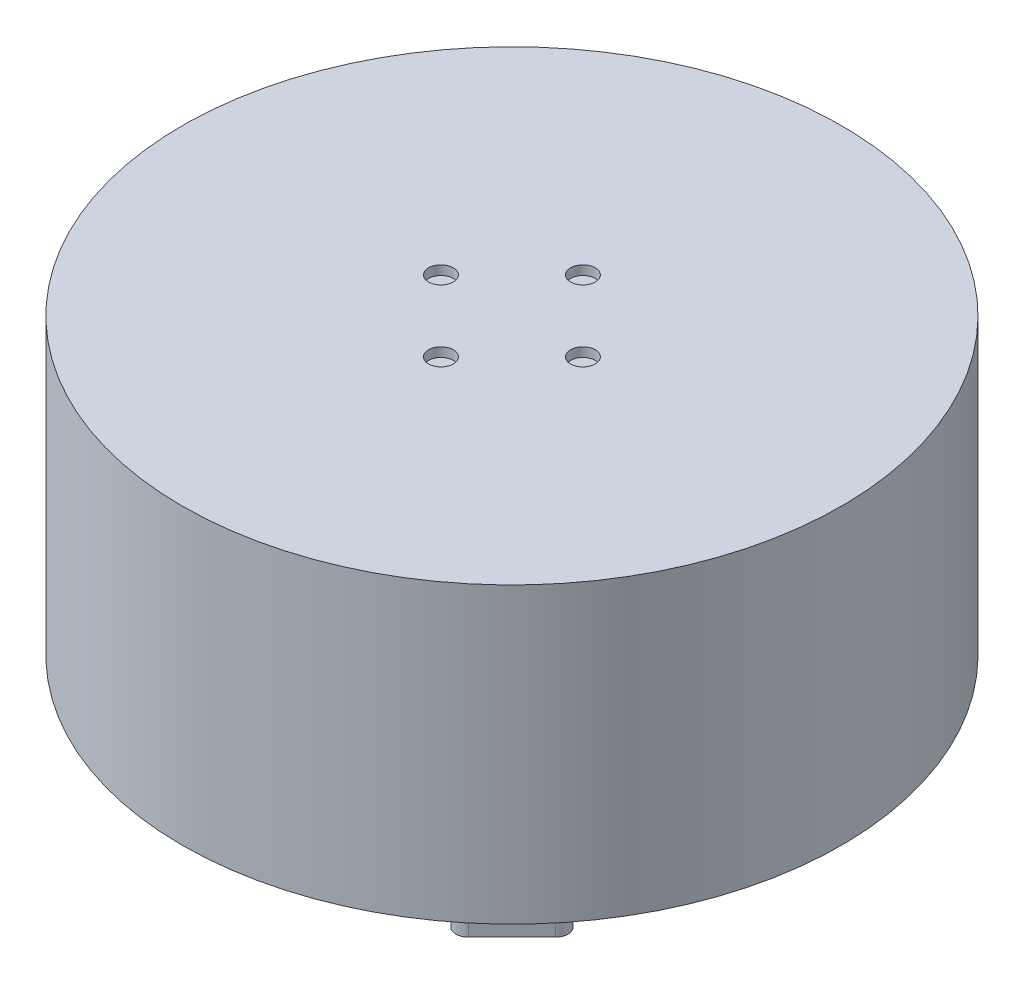
SolidWorks part; units mm, degrees
ref_plane "Front Plane" through (0, 0, 0) normal (0, 0, 1) x (1, 0, 0)
ref_plane "Top Plane" through (0, 0, 0) normal (0, 1, 0) x (1, 0, 0)
ref_plane "Right Plane" through (0, 0, 0) normal (1, 0, 0) x (0, 0, -1)
sketch "Sketch1" plane through (0, 0, 0) normal (0, 1, 0) x (1, 0, 0)
  circle A0 centre (0, 0) radius 53.4
  dimension "D1" = 106.8
extrude "Boss-Extrude1" add sketch "Sketch1" along normal blind 47.6
sketch "Sketch2" plane through (0, 0, 0) normal (0, -1, 0) x (1, 0, 0)
  circle A0 centre (0, 0) radius 20 construction
  circle A1 centre (0, 20) radius 2.5
  circle A2 centre (20, 0) radius 2.5
  circle A3 centre (0, -20) radius 2.5
  circle A4 centre (-20, 0) radius 2.5
  point P14 (0, 0)
  dimension "D1" = 40
  dimension "D2" = 5
  dimension "D3" = 4
extrude "Cut-Extrude1" cut sketch "Sketch2" against normal blind 1.5
sketch "Sketch3" plane through (0, 0, 0) normal (0, -1, 0) x (1, 0, 0)
  line L0 (0, 0) -> (0, 20) construction
  line L1 (0, 20) -> (20, 0) construction
  line L2 (20, 0) -> (0, 0) construction
  line L3 (0, 0) -> (32.1734, 32.1734) construction
  line L4 (28.6378, 35.7089) -> (35.7089, 28.6378) construction
  line L5 (30.7591, 37.8302) -> (37.8302, 30.7591) construction
  line L6 (26.5165, 33.5876) -> (33.5876, 26.5165) construction
  line L7 (30.052, 37.1231) -> (37.1231, 30.052)
  line L8 (27.2236, 34.2947) -> (34.2947, 27.2236)
  arc A0 (30.7591, 37.8302) -> (26.5165, 33.5876) centre (28.6378, 35.7089) ccw construction
  arc A1 (33.5876, 26.5165) -> (37.8302, 30.7591) centre (35.7089, 28.6378) ccw construction
  arc A2 (34.2947, 27.2236) -> (37.1231, 30.052) centre (35.7089, 28.6378) ccw
  arc A3 (30.052, 37.1231) -> (27.2236, 34.2947) centre (28.6378, 35.7089) ccw
  point P9 (32.1734, 32.1734)
  dimension "D3" = 3
  dimension "D1" = 45.5
  dimension "D2" = 10
  dimension "D4" = 1
extrude "Boss-Extrude2" add sketch "Sketch3" along normal blind 6
sketch "Sketch4" plane through (0, 47.6, 0) normal (0, 1, 0) x (1, 0, 0)
  circle A0 centre (0, 0) radius 11.5 construction
  circle A1 centre (0, 11.5) radius 2
  circle A2 centre (11.5, 0) radius 2
  circle A3 centre (0, -11.5) radius 2
  circle A4 centre (-11.5, 0) radius 2
  point P14 (0, 0)
  dimension "D3" = 4
  dimension "D1" = 23
  dimension "D2" = 4
extrude "Cut-Extrude2" cut sketch "Sketch4" against normal blind 1.5
equation "\"Np_b\" = 40"
equation "\"module\" = 0.7"
equation "\"pressure angle\" = 20.0"
equation "\"h_a\" = 0.7"
equation "\"h_b\" = 0.875"
equation "\"clr_tip_root\" = 0.17500000000000004"
equation "\"fw_p_s\" = 25.912913082891553"
equation "\"Nr_s\" = 116"
equation "\"pressure_angle\" = 20.0"
equation "\"h_f\" = 0.875"
equation "\"dp_r_s\" = 81.19999999999999"
equation "\"db_r_s\" = 76.30304080781575"
equation "\"fw_r_s\" = 24.412913082891553"
equation "\"alpha_r_s\" = 0.8539582918412556"
equation "\"beta_r_s\" = 3.259640721613546"
equation "\"bearing_ID\" = 70"
equation "\"bearing_OD\" = 90"
equation "\"bearing_height\" = 10"
equation "\"clearance_planet\" = 1.5"
equation "\"case_dist\" = 6.5"
equation "\"Motor_case_OD_max\" = 131.3"
equation "\"case_mounting_PCD\" = 123.8"
equation "\"bearing mount thickness\" = 8"
equation "\"case_mounting_hole_dia\" = 3"
equation "\"output_mounting_PCD\" = 98"
equation "\"output_mounting_hole_dia\" = 4"
equation "\"clearance_case_mount_holes_shell_thickness\" = 1"
equation "\"motor_case_OD_base\" = 121.8"
equation "\"sec_carrier_thickness\" = 5"
equation "\"sun_coupler_hub_thickness\" = 4"
equation "\"clearance_sun_coupler_sec_carrier\" = 1.5"
equation "\"clearance_motor_and_case\" = 5"
equation "\"motor_OD\" = 106.8"
equation "\"Motor_case_thickness\" = 2.5"
equation "\"Motor_case_ID\" = 116.8"
equation "\"case_mounting_hole_shift\" = 1.0"
equation "\"output_mounting_nut_wrench_size\" = 7"
equation "\"output_mounting_nut_thickness\" = 3.2"
equation "\"case_mounting_hole_allen_socket_dia\" = 5.5"
equation "\"output_mounting_nut_depth\" = 3"
equation "\"case_mounting_bolt_depth\" = 4.5"
equation "\"Ns\" = 48"
equation "\"ring_radial_thickness\" = 5"
equation "\"ring_OD\"= \"Nr_s\" * \"module\" + \"ring_radial_thickness\" * 2"
equation "\"ring_to_chamfer_clearance\" = 1.5"
equation "\"Motor_case_OD_base_to_chamfer\" = 5"
equation "\"pattern_offset_from_motor_case_OD_base\" = 3"
equation "\"pattern_bulge_dia\" = 3"
equation "\"pattern_num_bulge\" = 18"
equation "\"pattern_depth\" = 2"
equation "\"motor_height\" = 47.6"
equation "\"case_mounting_wrench_size\" = 5.5"
equation "\"case_mounting_nut_clearance\" = 2"
equation "\"base_plate_thickness\" = 4"
equation "\"case_mounting_nut_thickness\" = 2.4"
equation "\"case_mounting_surface_height\" = 4"
equation "\"motor_mount_hole_PCD\" = 40"
equation "\"motor_mount_hole_dia\" = 5"
equation "\"motor_mount_hole_num\" = 4"
equation "\"central_hole_offset_from_motor_mount_PCD\" = 5"
equation "\"wire_slot_dist_from_center\" = 45.5"
equation "\"wire_slot_length\" = 10"
equation "\"wire_slot_radius\" = 3"
equation "\"driver_upper_holes_dist_from_center\" = 29"
equation "\"driver_lower_holes_dist_from_center\" = 13"
equation "\"driver_side_holes_dist_from_center\" = 22.5"
equation "\"driver_mount_holes_dia\" = 3"
equation "\"driver_mount_inserts_OD\" = 4.8"
equation "\"driver_mount_thickness\" = 1.5"
equation "\"driver_mount_height\" = 6"
equation "\"air_flow_hole_offset\" = 3"
equation "\"num_planet\" = 4"
equation "\"planet_pin_bolt_dia\" = 5"
equation "\"planet_pin_socket_head_dia\" = 8.5"
equation "\"carrier_PCD\" = 61.599999999999994"
equation "\"planet_shaft_dia\" = 8"
equation "\"planet_shaft_step_offset\" = 1"
equation "\"carrier_trapezoidal_support_sun_offset\" = 5"
equation "\"carrier_trapezoidal_support_hole_PCD_offset_bearing_ID\" = 4"
equation "\"carrier_trapezoidal_support_hole_dia\" = 3"
equation "\"carrier_trapezoidal_support_hole_socket_head_dia\" = 5.5"
equation "\"carrier_bearing_step_width\" = 1.5"
equation "\"standard_clearance_1_5mm\" = 1.5"
equation "\"standard_fillet_1_5mm\" = 1.5"
equation "\"sun_shaft_bearing_OD\" = 16"
equation "\"sun_shaft_bearing_width\" = 5"
equation "\"standard_bearing_insertion_chamfer\" = 0.5"
equation "\"carrier_trapezoidal_support_hole_wrench_size\" = 5.5"
equation "\"planet_pin_bolt_wrench_size\" = 8"
equation "\"planet_bearing_OD\" = 12"
equation "\"planet_bearing_width\" = 3.5"
equation "\"planet_bore\" = 10"
equation "\"D1@Boss-Extrude1\"=\"motor_height\""
equation "\"D1@Sketch1\"=\"motor_OD\""
equation "\"D1@Sketch2\"=\"motor_mount_hole_PCD\""
equation "\"D2@Sketch2\"=\"motor_mount_hole_dia\""
equation "\"D3@Sketch2\"=\"motor_mount_hole_num\""
equation "\"D1@Cut-Extrude1\"=\"standard_clearance_1_5mm\""
equation "\"D1@Sketch3\"=\"wire_slot_dist_from_center\""
equation "\"D2@Sketch3\"=\"wire_slot_length\""
equation "\"D3@Sketch3\"=\"wire_slot_radius\""
equation "\"D1@Boss-Extrude2\"=\"standard_clearance_1_5mm\"*4"
equation "\"motor_output_hole_PCD\" = 23"
equation "\"motor_output_hole_dia\" = 4"
equation "\"motor_output_hole_num\" = 4"
equation "\"D1@Sketch4\"=\"motor_output_hole_PCD\""
equation "\"D2@Sketch4\"=\"motor_output_hole_dia\""
equation "\"D3@Sketch4\"=\"motor_output_hole_num\""
equation "\"D1@Cut-Extrude2\"=\"standard_clearance_1_5mm\""
equation "\"dp_s\" = 33.599999999999994"
equation "\"db_s\" = 31.57367205840652"
equation "\"fw_s_calc\" = 5.685933367726717"
equation "\"alpha_s\" = 0.8539582918412343"
equation "\"beta_s\" = 2.0420834163175314"
equation "\"dp_p_b\" = 28.0"
equation "\"db_p_b\" = 26.311393382005434"
equation "\"alpha_p_b\" = 0.8539582918412485"
equation "\"beta_p_b\" = 2.792083416317503"
equation "\"sun_shaft_bearing_ID\" = 8"
equation "\"sun_hub_dia\" = 30.0"
equation "\"sun_central_bolt_dia\" = 5"
equation "\"sun_central_bolt_socket_head_dia\" = 8.5"
equation "\"fw_s_used\" = 63.40868620995457"
equation "\"motor_output_hole_CSK_OD\" = 8"
equation "\"motor_output_hole_CSK_head_height\" = 2.0"
equation "\"bearing_retainer_thickness\" = 2"
equation "\"Np_s\" = 28"
equation "\"fw_p_b\" = 29.99577312706301"
equation "\"dp_p_s\" = 19.599999999999998"
equation "\"db_p_s\" = 18.417975367403802"
equation "\"alpha_p_s\" = 0.8539582918412592"
equation "\"beta_p_s\" = 4.7206548448889105"
equation "\"clr_tip_root_s\" = 0.17500000000000004"
equation "\"Nr_b\" = 128"
equation "\"fw_r_b\" = 29.99577312706301"
equation "\"dp_r_b\" = 89.6"
equation "\"db_r_b\" = 84.19645882241738"
equation "\"alpha_r_b\" = 0.8539582918412556"
equation "\"beta_r_b\" = 3.114166583682511"
equation "\"ring_OD_b\" = 99.6"
equation "\"small_ring_case_thickness\" = 4"
equation "\"carrier_thickness\" = 4"
equation "\"small_ring_output_wall_thickness\" = 5"
equation "\"small_ring_output_wall_to_bearing_shaft_attachement_hole_dia\" = 4"
equation "\"small_ring_output_wall_to_bearing_shaft_attachement_hole_depth\" = 6.5"
equation "\"small_ring_output_wall_to_bearing_shaft_attachement_nut_wrench\" = 7"
equation "\"small_ring_output_wall_to_bearing_shaft_attachement_nut_thickness\" = 3.2"
equation "\"small_ring_output_wall_to_bearing_shaft_attachement_hole_pcd\" = 12"
equation "\"small_ring_output_wall_to_bearing_shaft_attachement_hole_num\" = 3"
equation "\"small_ring_output_wall_to_bearing_shaft_attachement_hole_CSK_OD\" = 8"
equation "\"small_ring_output_wall_to_bearing_shaft_attachement_hole_CSK_head_height\" = 2.0"
equation "\"carrier_small_ring_inner_bearing_ID\" = 20"
equation "\"carrier_small_ring_inner_bearing_OD\" = 32"
equation "\"carrier_small_ring_inner_bearing_height\" = 7"
equation "\"carrier_small_ring_inner_bearing_flap\" = 2"
equation "\"gear_casing_big_ring_to_bearing_dist\" = 34.91291308289155"
equation "\"gear_casing_thickness\" = 4"
